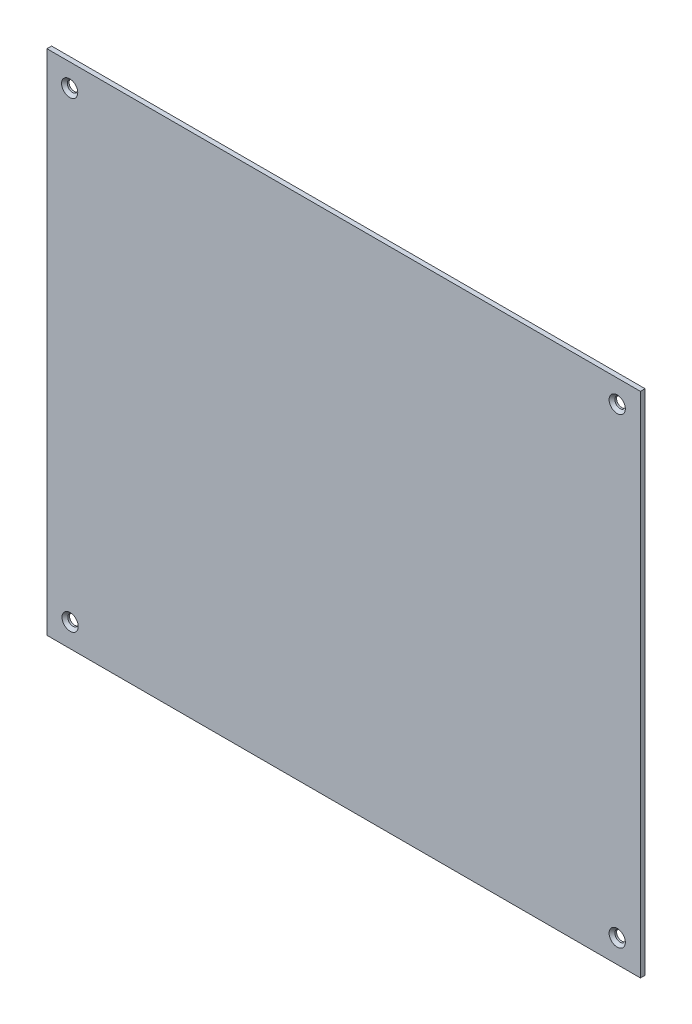
SolidWorks part; units mm, degrees
ref_plane "Front Plane" through (0, 0, 0) normal (0, 0, 1) x (1, 0, 0)
ref_plane "Top Plane" through (0, 0, 0) normal (0, 1, 0) x (1, 0, 0)
ref_plane "Right Plane" through (0, 0, 0) normal (1, 0, 0) x (0, 0, -1)
sketch "Sketch1" plane through (0, 0, 0) normal (0, 0, 1) x (1, 0, 0)
  line L1 (0, 0) -> (243.332, 0)
  line L2 (0, 0) -> (0, 208.28)
  line L3 (0, 208.28) -> (243.332, 208.28)
  line L11 (243.332, 0) -> (243.332, 208.28)
  dimension "D1" = 208.28
  dimension "D7" = 243.332
extrude "Boss-Extrude1" add sketch "Sketch1" along normal blind 1.905
sketch "Sketch4" plane through (0, 0, 1.905) normal (0, 0, 1) x (1, 0, 0)
  line L2 (233.807, 198.955) -> (243.332, 198.955) construction
  line L3 (243.332, 0) -> (243.332, 208.28) construction
  line L4 (233.807, 198.955) -> (233.807, 208.48) construction
  line L6 (0, 208.48) -> (243.332, 208.48) construction
  line L7 (0, 198.955) -> (9.325, 198.955) construction
  line L8 (0, 208.28) -> (0, 0) construction
  line L9 (9.325, 198.955) -> (9.325, 208.28) construction
  line L10 (243.332, 208.28) -> (0, 208.28) construction
  line L11 (0, 9.525) -> (9.525, 9.525) construction
  line L12 (9.525, 9.525) -> (9.525, 0) construction
  line L13 (0, 0) -> (243.332, 0) construction
  line L14 (233.807, 0) -> (233.807, 9.525) construction
  line L15 (233.807, 9.525) -> (243.332, 9.525) construction
  line L16 (243.332, 0) -> (243.332, 208.28) construction
  point P0 (9.325, 198.955)
  point P1 (233.807, 198.955)
  point P2 (233.807, 9.525)
  point P3 (9.525, 9.525)
  point P13 (233.807, 198.955)
  dimension "D2" = 9.525
hole_wizard "#6 Clearance Hole1" positions "Sketch4" profile "Sketch5" hole size "#6" standard "ANSI Inch" end condition up to next
sketch "Sketch5" plane through (9.325, 198.955, 1.905) normal (1, 0, 0) x (0, -1, 0)
  line L0 (0, 0) -> (0, 1.905)
  line L1 (0, 1.905) -> (2.1526, 1.905)
  line L2 (2.1526, 1.905) -> (2.1526, 1.1748)
  line L3 (2.1526, 1.1748) -> (3.3274, 0)
  line L5 (3.3274, 0) -> (0, 0)
  line L6 (-2.1526, 1.1747) -> (-3.3274, 0) construction
  line L11 (0, -6.35) -> (0, 107.95) construction
  dimension "Thru Hole Dia." = 4.3053
  dimension "Thru Hole Depth" = 1.905
  dimension "Near C'Sink Dia." = 6.6548
  dimension "Near C'Sink Angle" = 90
